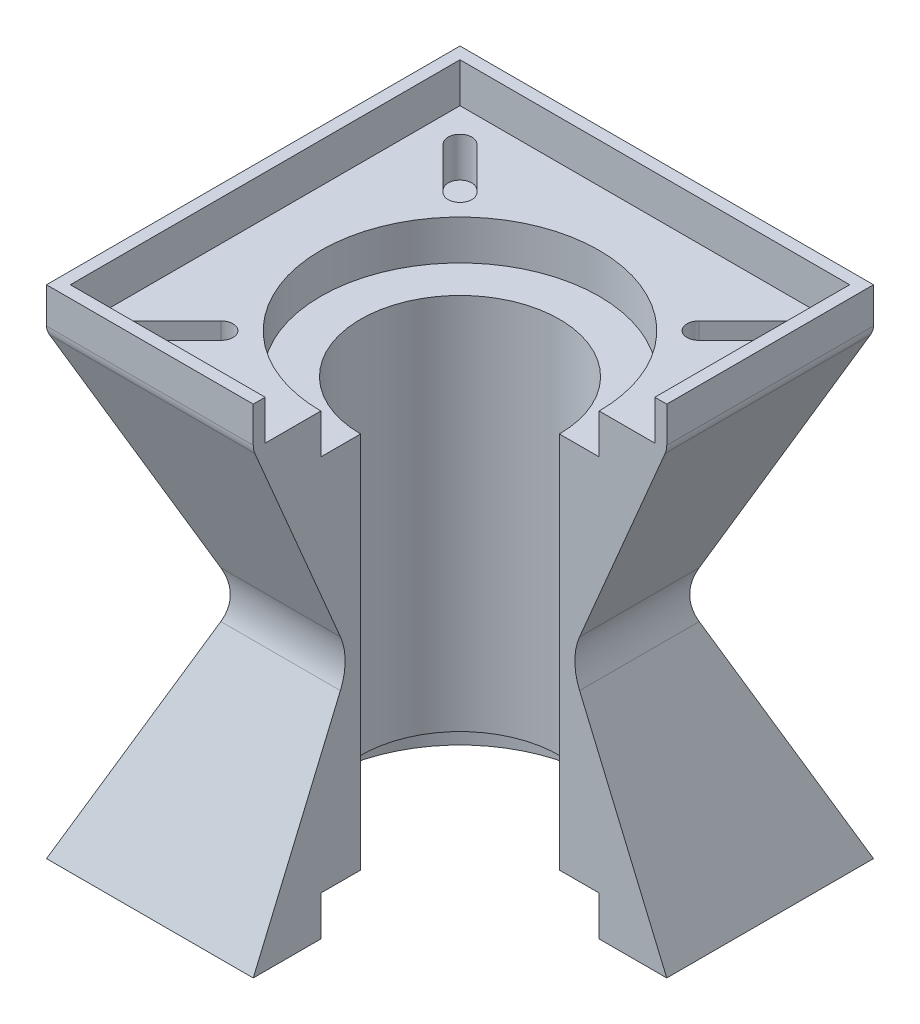
SolidWorks part; units mm, degrees
material "Cast Stainless Steel"
ref_plane "Front Plane" through (0, 0, 0) normal (0, 0, 1) x (1, 0, 0)
ref_plane "Top Plane" through (0, 0, 0) normal (0, 1, 0) x (1, 0, 0)
ref_plane "Right Plane" through (0, 0, 0) normal (1, 0, 0) x (0, 0, -1)
sketch "Sketch2" plane through (0, 0, 0) normal (0, 1, 0) x (1, 0, 0)
  line L1 (-52, -52) -> (52, -52)
  line L2 (-52, -52) -> (-52, 52)
  line L3 (-52, 52) -> (52, 52)
  line L4 (52, -52) -> (52, 52)
  line L5 (-52, -52) -> (52, 52) construction
  line L6 (-52, 52) -> (52, -52) construction
  point P0 (0, 0)
  dimension "D1" = 104
  dimension "D2" = 104
extrude "Boss-Extrude1" add sketch "Sketch2" along normal blind 57.5 draft 23
mirror "Mirror1" about plane through (0, 57.5, 0) normal (0, -1, 0) of bodies 101
sketch "Sketch3" plane through (0, 115, 0) normal (0, 1, 0) x (1, 0, 0)
  circle A0 centre (0, 0) radius 25
  dimension "D1" = 50
extrude "Cut-Extrude1" cut sketch "Sketch3" against normal through all
sketch "Sketch4" plane through (0, 115, 0) normal (0, 1, 0) x (1, 0, 0)
  line L1 (0, 0) -> (52, 0)
  line L2 (0, 0) -> (0, -52)
  line L3 (0, -52) -> (52, -52)
  line L4 (52, 0) -> (52, -52)
extrude "Cut-Extrude2" cut sketch "Sketch4" against normal through all
sketch "Sketch5" plane through (0, 115, 0) normal (0, 1, 0) x (1, 0, 0)
  circle A0 centre (0, 0) radius 35
  dimension "D1" = 70
extrude "Cut-Extrude3" cut sketch "Sketch5" against normal blind 10
sketch "Sketch6" plane through (0, 0, 0) normal (0, -1, 0) x (1, 0, 0)
  circle A0 centre (0, 0) radius 35
  dimension "D1" = 35
extrude "Cut-Extrude4" cut sketch "Sketch6" against normal blind 10
fillet "Fillet1" radius 15 3 edges at (27.5927, 57.5, -13.7963) (0, 57.5, -27.5927) (-27.5927, 57.5, 0)
fillet "Fillet2" radius 15 1 edges at (-14.4441, 57.5, 27.5927)
sketch "Sketch7" plane through (0, 115, 0) normal (0, 1, 0) x (1, 0, 0)
  line L6 (0, -52) -> (-52, -52)
  line L7 (-52, -52) -> (-52, 52)
  line L8 (-52, 52) -> (52, 52)
  line L9 (52, 52) -> (52, 0)
  line L10 (52, 0) -> (49, 0)
  line L11 (52, 0) -> (35, 0) construction
  line L12 (37.8814, 3) -> (49, 3)
  line L13 (49, 3) -> (49, 49)
  line L14 (49, 49) -> (-49, 49)
  line L15 (-49, 49) -> (-49, -49)
  line L16 (-49, -49) -> (-3, -49)
  line L17 (-3, -49) -> (-3, -37.8814)
  line L19 (49, 0) -> (49, 49)
  line L20 (49, 49) -> (-49, 49)
  line L21 (-49, 49) -> (-49, -49)
  line L22 (-49, -49) -> (0, -49)
  line L24 (0, -52) -> (0, -49)
  line L25 (0, -35) -> (0, -52) construction
  arc A2 (37.8814, 3) -> (-3, -37.8814) centre (0, 0) ccw
  point P2 (49, -0.2885)
  point P16 (-0.4553, -49)
  dimension "D1" = 3
extrude "Boss-Extrude2" add sketch "Sketch7" along normal blind 10
sketch "Sketch8" plane through (0, 115, 0) normal (0, 1, 0) x (1, 0, 0)
  line L0 (0, 0) -> (-35.3553, 35.3553) construction
  line L1 (-35.3553, 35.3553) -> (-52, 52) construction
  line L2 (-30.052, 30.052) -> (-40.6586, 40.6586) construction
  line L3 (-32.1734, 27.9307) -> (-42.78, 38.5373)
  line L4 (-27.9307, 32.1734) -> (-38.5373, 42.78)
  line L5 (30.052, 30.052) -> (40.6586, 40.6586) construction
  line L6 (27.9307, 32.1734) -> (38.5373, 42.78)
  line L7 (32.1734, 27.9307) -> (42.78, 38.5373)
  line L8 (30.052, -30.052) -> (40.6586, -40.6586) construction
  line L9 (32.1734, -27.9307) -> (42.78, -38.5373)
  line L10 (27.9307, -32.1734) -> (38.5373, -42.78)
  line L11 (-30.052, -30.052) -> (-40.6586, -40.6586) construction
  line L12 (-27.9307, -32.1734) -> (-38.5373, -42.78)
  line L13 (-32.1734, -27.9307) -> (-42.78, -38.5373)
  circle A0 centre (0, 0) radius 50 construction
  arc A1 (-32.1734, 27.9307) -> (-27.9307, 32.1734) centre (-30.052, 30.052) ccw
  arc A2 (-38.5373, 42.78) -> (-42.78, 38.5373) centre (-40.6586, 40.6586) ccw
  arc A3 (27.9307, 32.1734) -> (32.1734, 27.9307) centre (30.052, 30.052) ccw
  arc A4 (42.78, 38.5373) -> (38.5373, 42.78) centre (40.6586, 40.6586) ccw
  arc A5 (32.1734, -27.9307) -> (27.9307, -32.1734) centre (30.052, -30.052) ccw
  arc A6 (38.5373, -42.78) -> (42.78, -38.5373) centre (40.6586, -40.6586) ccw
  arc A7 (-27.9307, -32.1734) -> (-32.1734, -27.9307) centre (-30.052, -30.052) ccw
  arc A8 (-42.78, -38.5373) -> (-38.5373, -42.78) centre (-40.6586, -40.6586) ccw
  point P7 (-35.3553, 35.3553)
  point P14 (-38.5373, -41.2995)
  point P15 (0, 0)
  point P19 (35.3553, 35.3553)
  point P26 (35.3553, -35.3553)
  point P33 (-35.3553, -35.3553)
  point P38 (0, 0)
  dimension "D1" = 100
  dimension "D2" = 3
  dimension "D3" = 15
  dimension "D4" = 4
extrude "Cut-Extrude5" cut sketch "Sketch8" against normal blind 10
fillet "Fillet4" radius 5 4 edges at (52, 115, -26) (0, 115, -52) (-52, 115, 0) (-26, 115, 52)
equation "\"a\"= 115mm"
equation "\"b\"= 104mm"
equation "\"c\"= 23mm"
